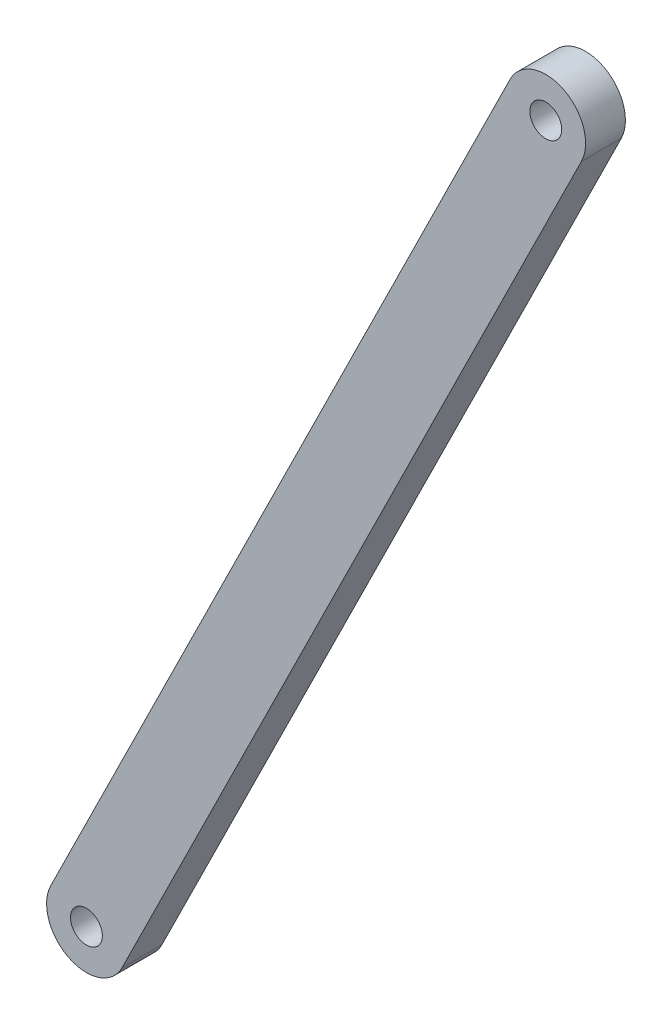
SolidWorks part; units mm, degrees
ref_plane "Front Plane" through (0, 0, 0) normal (0, 0, 1) x (1, 0, 0)
ref_plane "Top Plane" through (0, 0, 0) normal (0, 1, 0) x (1, 0, 0)
ref_plane "Right Plane" through (0, 0, 0) normal (1, 0, 0) x (0, 0, -1)
sketch "Sketch1" plane through (0, 0, 0) normal (0, 0, 1) x (1, 0, 0)
  line L0 (42.108, 122.3882) -> (-15.5641, 5.8811)
  line L1 (-24.5262, 10.3174) -> (33.1459, 126.8246)
  circle A0 centre (-20.0452, 8.0992) radius 2 construction
  circle A1 centre (-20.0452, 8.0992) radius 2
  circle A2 centre (37.627, 124.6064) radius 2 construction
  circle A3 centre (37.627, 124.6064) radius 2
  arc A4 (-15.5641, 5.8811) -> (-24.5262, 10.3174) centre (-20.0452, 8.0992) cw
  arc A5 (33.1459, 126.8246) -> (42.108, 122.3882) centre (37.627, 124.6064) cw
  dimension "D1" = 5
  dimension "D2" = 5
extrude "Boss-Extrude1" add sketch "Sketch1" along normal blind 5 from offset 5
